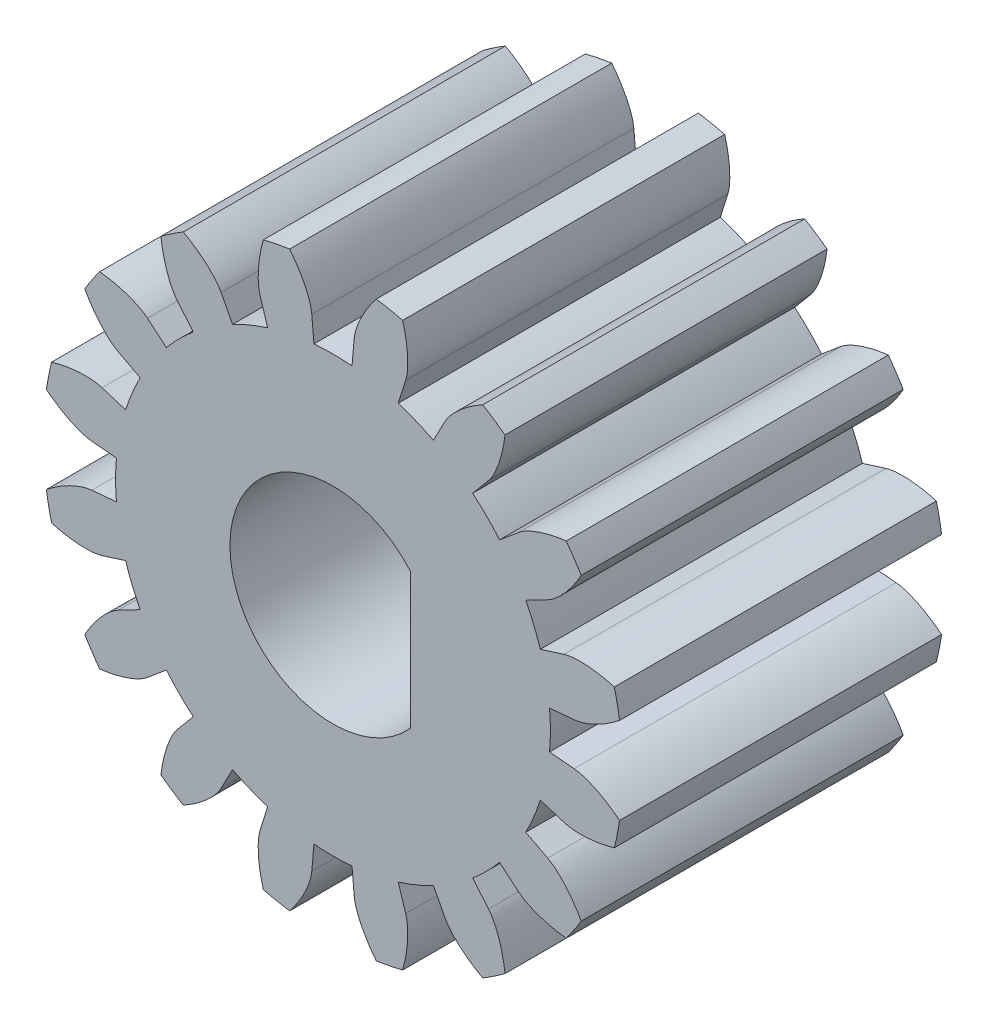
SolidWorks part; units mm, degrees
ref_plane "前视基准面" through (0, 0, 0) normal (0, 0, 1) x (1, 0, 0)
ref_plane "上视基准面" through (0, 0, 0) normal (0, 1, 0) x (1, 0, 0)
ref_plane "右视基准面" through (0, 0, 0) normal (1, 0, 0) x (0, 0, -1)
other "Configuration Table"
sketch "草图1" plane through (0, 0, 0) normal (0, 0, 1) x (1, 0, 0)
  line L0 (0, 0) -> (4, 0) construction
  line L1 (0, 0) -> (3.9807, 0.3921) construction
  line L2 (0, 0) -> (3.7443, 0.3291)
  line L3 (3.9807, 0.3921) -> (3.9807, -0.3921) construction
  line L4 (0, 0) -> (3.7443, -0.3291)
  circle A0 centre (0, 0) radius 4.5
  circle A1 centre (0, 0) radius 4 construction
  circle A2 centre (0, 0) radius 3.375
  circle A3 centre (0, 0) radius 3.7588 construction
  circle A4 centre (0, 0) radius 1.5
  spline S0 degree 4 poles (3.7443, 0.3291) (3.7729, 0.3316) (3.852, 0.3445) (3.9981, 0.3926) (4.2218, 0.5023) (4.4866, 0.6881) (4.7894, 0.9723) (5.0903, 1.3552) (5.3572, 1.8186) (5.6269, 2.4866) (5.7837, 3.1915) (5.8395, 3.939) (5.7839, 4.8292) (5.6145, 5.7064) (5.2709, 6.6864) (4.7256, 7.7028) (4.0402, 8.6299) (3.2362, 9.4556) (2.3338, 10.1718) (1.3511, 10.7732) (0.306, 11.2565) (-0.6502, 11.5751) (-1.4192, 11.7574) (-1.9866, 11.8556) (-2.3401, 11.9048) (-2.6306, 11.9368) (-2.9071, 11.9619) (-3.2112, 11.9792) (-3.4455, 11.9894) (-3.715, 11.9923) (-3.9867, 11.9914) (-4.2588, 11.9836) (-4.7357, 11.9589) (-5.1232, 11.9154) (-5.525, 11.8674) (-5.7188, 11.8311) (-5.8484, 11.8109) knots 0 0 0 0 0 0.005604 0.015718 0.02996 0.048734 0.068727 0.096889 0.125051 0.153212 0.209535 0.237696 0.271429 0.327752 0.384075 0.440398 0.496721 0.553044 0.609367 0.66569 0.722013 0.778336 0.806497 0.820578 0.834659 0.84874 0.86282 0.876901 0.890982 0.900036 0.909091 0.931818 0.954545 0.977273 1 1 1 1 1 construction
  spline S1 degree 4 poles (3.7443, 0.3291) (3.7729, 0.3316) (3.852, 0.3445) (3.9981, 0.3926) (4.2218, 0.5023) (4.4866, 0.6881) (4.7894, 0.9723) (5.0903, 1.3552) (5.3572, 1.8186) (5.6269, 2.4866) (5.7837, 3.1915) (5.8395, 3.939) (5.7839, 4.8292) (5.6145, 5.7064) (5.2709, 6.6864) (4.7256, 7.7028) (4.0402, 8.6299) (3.2362, 9.4556) (2.3338, 10.1718) (1.3511, 10.7732) (0.306, 11.2565) (-0.6502, 11.5751) (-1.4192, 11.7574) (-1.9866, 11.8556) (-2.3401, 11.9048) (-2.6306, 11.9368) (-2.9071, 11.9619) (-3.2112, 11.9792) (-3.4455, 11.9894) (-3.715, 11.9923) (-3.8743, 11.9918) (-3.9585, 11.9906) (-4.0005, 11.9898) knots 0 0 0 0 0 0.005604 0.015718 0.02996 0.048734 0.068727 0.096889 0.125051 0.153212 0.209535 0.237696 0.271429 0.327752 0.384075 0.440398 0.496721 0.553044 0.609367 0.66569 0.722013 0.778336 0.806497 0.820578 0.834659 0.84874 0.86282 0.876901 0.890982 0.900036 0.909091 0.909091 0.909091 0.909091 0.909091
  spline S2 degree 4 poles (3.7443, -0.3291) (3.7729, -0.3316) (3.852, -0.3445) (3.9981, -0.3926) (4.2218, -0.5023) (4.4866, -0.6881) (4.7894, -0.9723) (5.0903, -1.3552) (5.3572, -1.8186) (5.6269, -2.4866) (5.7837, -3.1915) (5.8395, -3.939) (5.7839, -4.8292) (5.6145, -5.7064) (5.2709, -6.6864) (4.7256, -7.7028) (4.0402, -8.6299) (3.2362, -9.4556) (2.3338, -10.1718) (1.3511, -10.7732) (0.306, -11.2565) (-0.6502, -11.5751) (-1.4192, -11.7574) (-1.9866, -11.8556) (-2.3401, -11.9048) (-2.6306, -11.9368) (-2.9071, -11.9619) (-3.2112, -11.9792) (-3.4455, -11.9894) (-3.715, -11.9923) (-3.9867, -11.9914) (-4.2588, -11.9836) (-4.7357, -11.9589) (-5.1232, -11.9154) (-5.525, -11.8674) (-5.7188, -11.8311) (-5.8484, -11.8109) knots 0 0 0 0 0 0.005604 0.015718 0.02996 0.048734 0.068727 0.096889 0.125051 0.153212 0.209535 0.237696 0.271429 0.327752 0.384075 0.440398 0.496721 0.553044 0.609367 0.66569 0.722013 0.778336 0.806497 0.820578 0.834659 0.84874 0.86282 0.876901 0.890982 0.900036 0.909091 0.931818 0.954545 0.977273 1 1 1 1 1 construction
  spline S3 degree 4 poles (3.7443, -0.3291) (3.7729, -0.3316) (3.852, -0.3445) (3.9981, -0.3926) (4.2218, -0.5023) (4.4866, -0.6881) (4.7894, -0.9723) (5.0903, -1.3552) (5.3572, -1.8186) (5.6269, -2.4866) (5.7837, -3.1915) (5.8395, -3.939) (5.7839, -4.8292) (5.6145, -5.7064) (5.2709, -6.6864) (4.7256, -7.7028) (4.0402, -8.6299) (3.2362, -9.4556) (2.3338, -10.1718) (1.3511, -10.7732) (0.306, -11.2565) (-0.6502, -11.5751) (-1.4192, -11.7574) (-1.9866, -11.8556) (-2.3401, -11.9048) (-2.6306, -11.9368) (-2.9071, -11.9619) (-3.2112, -11.9792) (-3.4455, -11.9894) (-3.715, -11.9923) (-3.8743, -11.9918) (-3.9585, -11.9906) (-4.0005, -11.9898) knots 0 0 0 0 0 0.005604 0.015718 0.02996 0.048734 0.068727 0.096889 0.125051 0.153212 0.209535 0.237696 0.271429 0.327752 0.384075 0.440398 0.496721 0.553044 0.609367 0.66569 0.722013 0.778336 0.806497 0.820578 0.834659 0.84874 0.86282 0.876901 0.890982 0.900036 0.909091 0.909091 0.909091 0.909091 0.909091
  point P15 (3.9807, 0)
  dimension "齿顶圆直径" = 9
  dimension "分度圆直径" = 8
  dimension "齿根圆直径" = 6.75
  dimension "基圆直径" = 7.5175
  dimension "内孔直径" = 3
  dimension "渐近线镜像线夹角" = 5.625
extrude "凸台-拉伸1" add sketch "草图1" along normal blind 5 contours A0 | A4
extrude "切除-拉伸1" cut sketch "草图1<3>" along normal through all contours A2 S3 A0 S1 region at (4.0116, 0, 0)
sketch "草图1<3>" plane through (0, 0, 0) normal (0, 0, 1) x (1, 0, 0) same geometry as "草图1"
pattern_circular "阵列(圆周)1" count 16 every 22.5 about axis through (0, 0, 5) along (0, 0, 1) of "切除-拉伸1"
sketch "草图2" plane through (0, 0, 5) normal (0, 0, 1) x (1, 0, 0)
  line L0 (1.2, 1.0583) -> (1.2, -1.0583)
  circle A0 centre (0, 0) radius 1.6
  dimension "D1" = 3.2
  dimension "D2" = 1.2
extrude "凸台-拉伸2" add sketch "草图2" against normal through all contours A0
extrude "切除-拉伸2" cut sketch "草图2<3>" against normal through all contours L0 A0 region at (-0.1059, 0, 5)
sketch "草图2<3>" plane through (0, 0, 5) normal (0, 0, 1) x (1, 0, 0) same geometry as "草图2"
equation "\"m\"= 0.5'模数"
equation "\"z\"= 16'齿数"
equation "\"a\"= 20度'压力角"
equation "\"d\"= \"m\" * \"z\"'分度圆直径"
equation "\"da\"= ( \"z\" + 2 ) * \"m\"'齿顶圆直径"
equation "\"df\"= ( \"z\" - 2.5 ) * \"m\"'齿根圆直径"
equation "\"s\"= 0.5 * PI * \"m\"'分度圆齿厚"
equation "\"r\"= 0.38 * \"m\"'齿根圆角"
equation "\"B\"= 0.3 * \"d\"'齿厚"
equation "\"db\"= \"m\" * \"z\" * cos ( \"a\" )'基圆直径"
equation "\"rb\"= \"db\" / 2'基圆半径"
equation "\"齿顶圆直径@草图1\"= \"da\""
equation "\"分度圆直径@草图1\"= \"d\""
equation "\"齿根圆直径@草图1\"= \"df\""
equation "\"基圆直径@草图1\"= \"db\""
equation "\"渐近线镜像线夹角@草图1\"= 360 / 4 / \"z\""
equation "\"h\"= 5'齿轮厚度"
equation "\"ir\"= 3'内孔直径"
equation "\"内孔直径@草图1\"= \"ir\""
equation "\"齿轮厚@凸台-拉伸1\"= \"h\""
equation "\"齿轮夹角@阵列(圆周)1\"= 360 / \"z\""
equation "\"齿数@阵列(圆周)1\"= \"z\""
